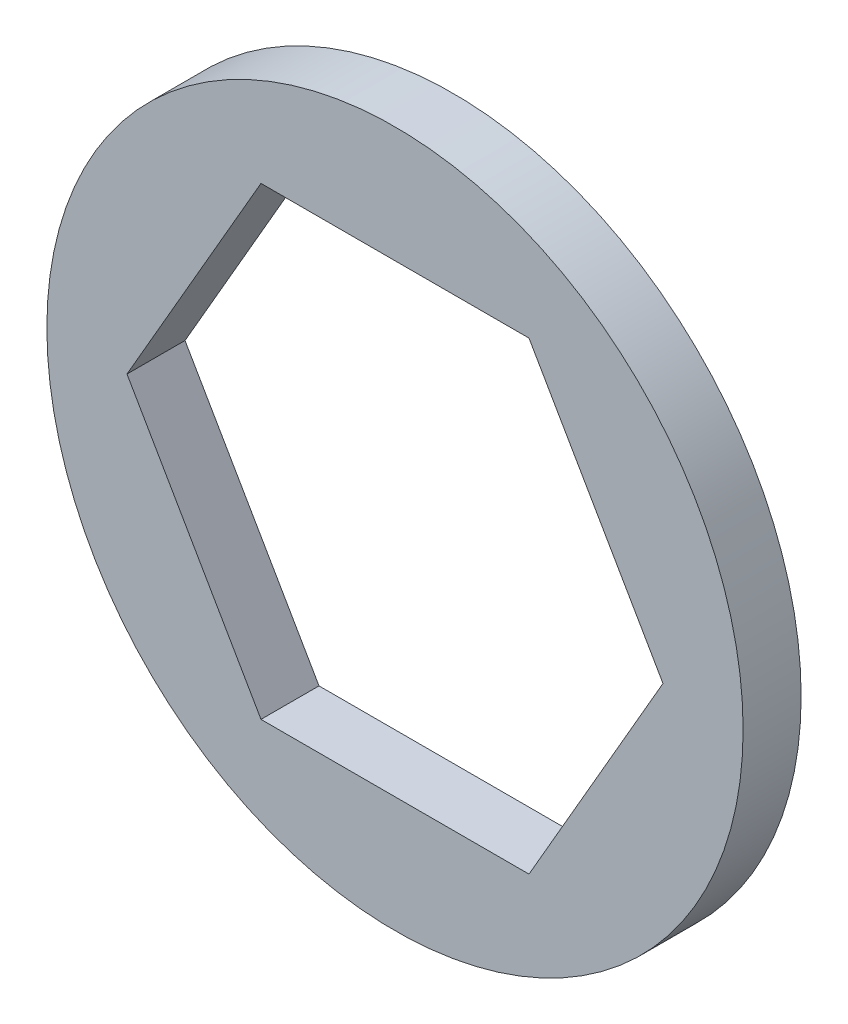
SolidWorks part; units mm, degrees
material "PET"
ref_plane "Front Plane" through (0, 0, 0) normal (0, 0, 1) x (1, 0, 0)
ref_plane "Top Plane" through (0, 0, 0) normal (0, 1, 0) x (1, 0, 0)
ref_plane "Right Plane" through (0, 0, 0) normal (1, 0, 0) x (0, 0, -1)
sketch "Sketch1" plane through (0, 0, 0) normal (0, 0, 1) x (1, 0, 0)
  line L1 (7.3323, 0) -> (3.6662, 6.35)
  line L2 (3.6662, 6.35) -> (-3.6662, 6.35)
  line L3 (-3.6662, 6.35) -> (-7.3323, 0)
  line L4 (-7.3323, 0) -> (-3.6662, -6.35)
  line L5 (-3.6662, -6.35) -> (3.6662, -6.35)
  line L6 (3.6662, -6.35) -> (7.3323, 0)
  circle A0 centre (0, 0) radius 9.525
  circle A1 centre (0, 0) radius 6.35 construction
  point P3 (0, 0)
  dimension "D1" = 12.7
  dimension "D2" = 19.05
extrude "Boss-Extrude1" add sketch "Sketch1" along normal blind 1.5875
